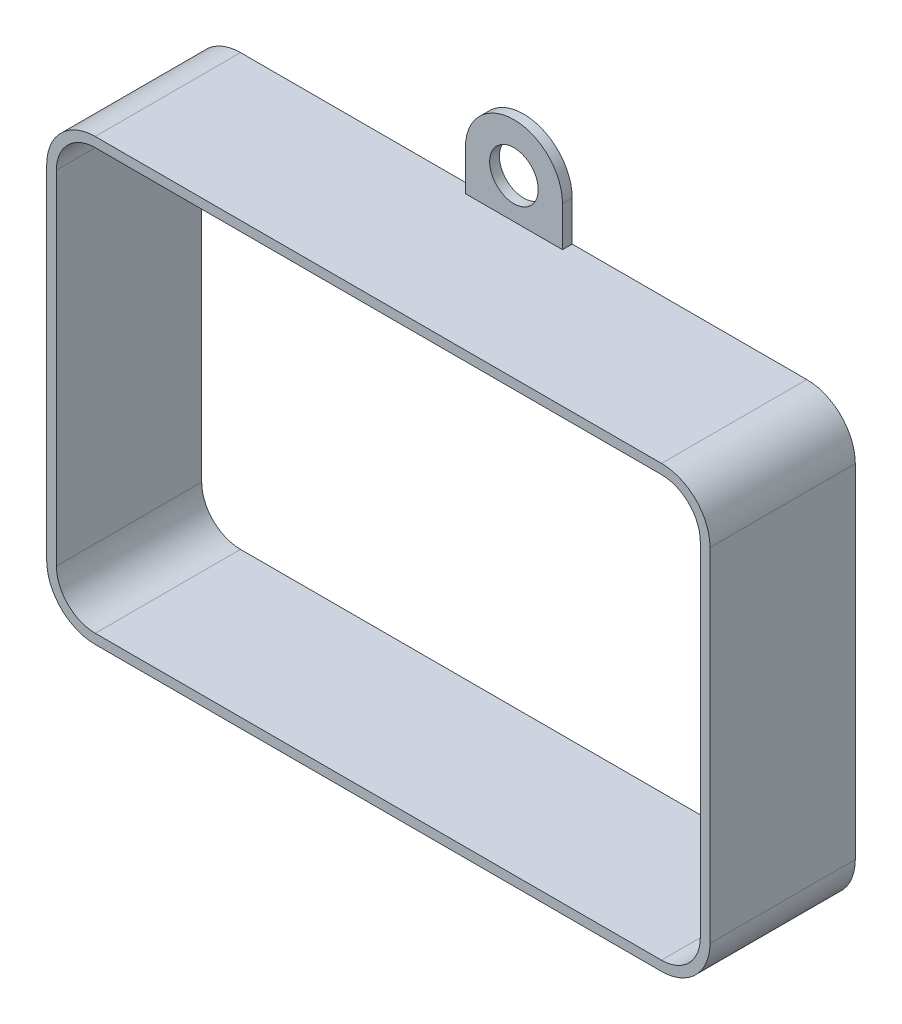
SolidWorks part; units mm, degrees
ref_plane "Front Plane" through (0, 0, 0) normal (0, 0, 1) x (1, 0, 0)
ref_plane "Top Plane" through (0, 0, 0) normal (0, 1, 0) x (1, 0, 0)
ref_plane "Right Plane" through (0, 0, 0) normal (1, 0, 0) x (0, 0, -1)
sketch "Sketch1" plane through (0, 0, 0) normal (0, 0, 1) x (1, 0, 0)
  line L1 (-14.575, -11.325) -> (14.575, -11.325)
  line L2 (-17.075, -8.825) -> (-17.075, 8.825)
  line L3 (-14.575, 11.325) -> (14.575, 11.325)
  line L4 (17.075, -8.825) -> (17.075, 8.825)
  line L5 (-17.075, -11.325) -> (17.075, 11.325) construction
  line L6 (-17.075, 11.325) -> (17.075, -11.325) construction
  line L8 (-16.575, 10.825) -> (-17.075, 10.825) construction
  line L9 (14.575, -10.825) -> (-14.575, -10.825)
  line L10 (16.575, -8.825) -> (16.575, 8.825)
  line L11 (14.575, 10.825) -> (-14.575, 10.825)
  line L12 (-16.575, -8.825) -> (-16.575, 8.825)
  line L13 (16.575, -10.825) -> (-16.575, 10.825) construction
  line L14 (16.575, 10.825) -> (-16.575, -10.825) construction
  line L15 (-16.575, 10.825) -> (-16.575, 11.325) construction
  line L16 (-16.375, 9.825) -> (-16.375, -9.825) construction
  line L17 (16.375, 9.825) -> (-16.375, 9.825) construction
  line L18 (-2.5, 13.375) -> (-2.5, 11.325)
  line L19 (2.5, 13.375) -> (2.5, 11.325)
  line L20 (-2.5, -13.375) -> (-2.5, -11.325)
  line L21 (2.5, -13.375) -> (2.5, -11.325)
  line L22 (-20.75, 2.5) -> (-17.075, 2.5)
  line L23 (-20.75, -2.5) -> (-17.075, -2.5)
  arc A0 (-14.575, -10.825) -> (-16.575, -8.825) centre (-14.575, -8.825) cw
  arc A1 (-2.4744, -13.0179) -> (2.4744, -13.0179) centre (0, -13.375) ccw construction
  arc A2 (14.575, -10.825) -> (16.575, -8.825) centre (14.575, -8.825) ccw
  arc A3 (16.575, 8.825) -> (14.575, 10.825) centre (14.575, 8.825) ccw
  arc A4 (-20.3929, 2.4744) -> (-20.3929, -2.4744) centre (-20.75, 0) ccw construction
  arc A5 (-14.575, 10.825) -> (-16.575, 8.825) centre (-14.575, 8.825) ccw
  arc A6 (-14.575, -11.325) -> (-17.075, -8.825) centre (-14.575, -8.825) cw
  arc A7 (14.575, -11.325) -> (17.075, -8.825) centre (14.575, -8.825) ccw
  arc A8 (2.4744, 13.0179) -> (-2.4744, 13.0179) centre (0, 13.375) ccw construction
  circle A9 centre (-20.75, 0) radius 1.25
  arc A10 (-2.4744, -13.0179) -> (2.4744, -13.0179) centre (0, -13.375) ccw
  circle A11 centre (0, 13.375) radius 1.25
  circle A12 centre (0, -13.375) radius 1.25
  arc A13 (-20.3929, 2.4744) -> (-20.3929, -2.4744) centre (-20.75, 0) ccw
  arc A14 (14.575, 11.325) -> (17.075, 8.825) centre (14.575, 8.825) cw
  arc A15 (-17.075, 8.825) -> (-14.575, 11.325) centre (-14.575, 8.825) cw
  arc A17 (2.4744, 13.0179) -> (-2.4744, 13.0179) centre (0, 13.375) ccw
  point P0 (0, 0)
  point P31 (0, 0)
  dimension "D4" = 2.5
  dimension "D5" = 2
  dimension "D6" = 2.5
  dimension "D1" = 0.5
  dimension "D2" = 0.2
  dimension "D3" = 1
extrude "Boss-Extrude1" add sketch "Sketch1" along normal offset from surface (7.48 mm away) 0.5 contours A13 L2 | L1 L4 L3 L2 L9 L12 L11 L10 | A17 L3 | A10 L1 region at (-16.053, -10.303, 0) region at (0, -11.3926, 0) region at (-18.9125, -2.4205, 0) region at (-2.4324, 12.35, 0) offset beyond the face yes
sketch "Sketch2" plane through (0, 0, 7.48) normal (0, 0, 1) x (1, 0, 0)
  line L0 (-2.5, 11.325) -> (2.5, 11.325)
  line L1 (-17.075, 2.5) -> (-17.075, -2.5)
  line L2 (-2.5, -11.325) -> (2.5, -11.325)
  line L13 (-17.075, 2.5) -> (-20.75, 2.5)
  line L14 (-20.75, -2.5) -> (-17.075, -2.5)
  line L15 (-17.075, -2.5) -> (-17.075, -8.825)
  line L16 (-14.575, -11.325) -> (-2.5, -11.325)
  line L17 (-2.5, -11.325) -> (-2.5, -13.375)
  line L18 (2.5, -13.375) -> (2.5, -11.325)
  line L19 (2.5, -11.325) -> (14.575, -11.325)
  line L20 (17.075, -8.825) -> (17.075, 8.825)
  line L21 (14.575, 11.325) -> (2.5, 11.325)
  line L22 (2.5, 11.325) -> (2.5, 13.375)
  line L23 (-2.5, 13.375) -> (-2.5, 11.325)
  line L24 (-2.5, 11.325) -> (-14.575, 11.325)
  line L25 (-17.075, 8.825) -> (-17.075, 2.5)
  line L26 (-17.075, 2.5) -> (-20.75, 2.5)
  line L27 (-20.75, -2.5) -> (-17.075, -2.5)
  line L28 (-17.075, -2.5) -> (-17.075, -8.825)
  line L29 (-14.575, -11.325) -> (-2.5, -11.325)
  line L30 (-2.5, -11.325) -> (-2.5, -13.375)
  line L31 (2.5, -13.375) -> (2.5, -11.325)
  line L32 (2.5, -11.325) -> (14.575, -11.325)
  line L33 (17.075, -8.825) -> (17.075, 8.825)
  line L34 (14.575, 11.325) -> (2.5, 11.325)
  line L35 (2.5, 11.325) -> (2.5, 13.375)
  line L36 (-2.5, 13.375) -> (-2.5, 11.325)
  line L37 (-2.5, 11.325) -> (-14.575, 11.325)
  line L38 (-17.075, 8.825) -> (-17.075, 2.5)
  arc A7 (-20.75, 2.5) -> (-20.75, -2.5) centre (-20.75, 0) ccw
  arc A8 (-17.075, -8.825) -> (-14.575, -11.325) centre (-14.575, -8.825) ccw
  arc A9 (-2.5, -13.375) -> (2.5, -13.375) centre (0, -13.375) ccw
  arc A10 (14.575, -11.325) -> (17.075, -8.825) centre (14.575, -8.825) ccw
  arc A11 (17.075, 8.825) -> (14.575, 11.325) centre (14.575, 8.825) ccw
  arc A12 (2.5, 13.375) -> (-2.5, 13.375) centre (0, 13.375) ccw
  arc A13 (-14.575, 11.325) -> (-17.075, 8.825) centre (-14.575, 8.825) ccw
  arc A14 (-20.75, 2.5) -> (-20.75, -2.5) centre (-20.75, 0) ccw
  arc A15 (-17.075, -8.825) -> (-14.575, -11.325) centre (-14.575, -8.825) ccw
  arc A16 (-2.5, -13.375) -> (2.5, -13.375) centre (0, -13.375) ccw
  arc A17 (14.575, -11.325) -> (17.075, -8.825) centre (14.575, -8.825) ccw
  arc A18 (17.075, 8.825) -> (14.575, 11.325) centre (14.575, 8.825) ccw
  arc A19 (2.5, 13.375) -> (-2.5, 13.375) centre (0, 13.375) ccw
  arc A20 (-14.575, 11.325) -> (-17.075, 8.825) centre (-14.575, 8.825) ccw
  arc M18 (-20.75, 2.5) -> (-20.75, -2.5) centre (-20.75, 0) ccw
  arc M23 (-2.5, -13.375) -> (2.5, -13.375) centre (0, -13.375) ccw
  arc M29 (2.5, 13.375) -> (-2.5, 13.375) centre (0, 13.375) ccw
  circle M57 centre (0, 13.375) radius 1.25
  circle M62 centre (-20.75, 0) radius 1.25
  line M63 (-17.075, 2.5) -> (-20.75, 2.5)
  line M64 (-20.75, -2.5) -> (-17.075, -2.5)
  line M68 (-2.5, -11.325) -> (-2.5, -13.375)
  line M69 (2.5, -13.375) -> (2.5, -11.325)
  line M74 (2.5, 11.325) -> (2.5, 13.375)
  line M75 (-2.5, 13.375) -> (-2.5, 11.325)
  circle M79 centre (0, -13.375) radius 1.25
  dimension "D1" = 0
extrude "Cut-Extrude1" cut sketch "Sketch2" against normal offset from surface (6.98 mm away) 0.5 contours L0 M75 M74 M29 M57 | L1 M63 M18 M64 M62 | L2 M68 M23 M69 M79 region at (-2.4324, 12.35, 7.48) region at (-17.1545, 0, 7.48) region at (2.4324, -12.35, 7.48) up to face at (-3.9075, 0, 0)
